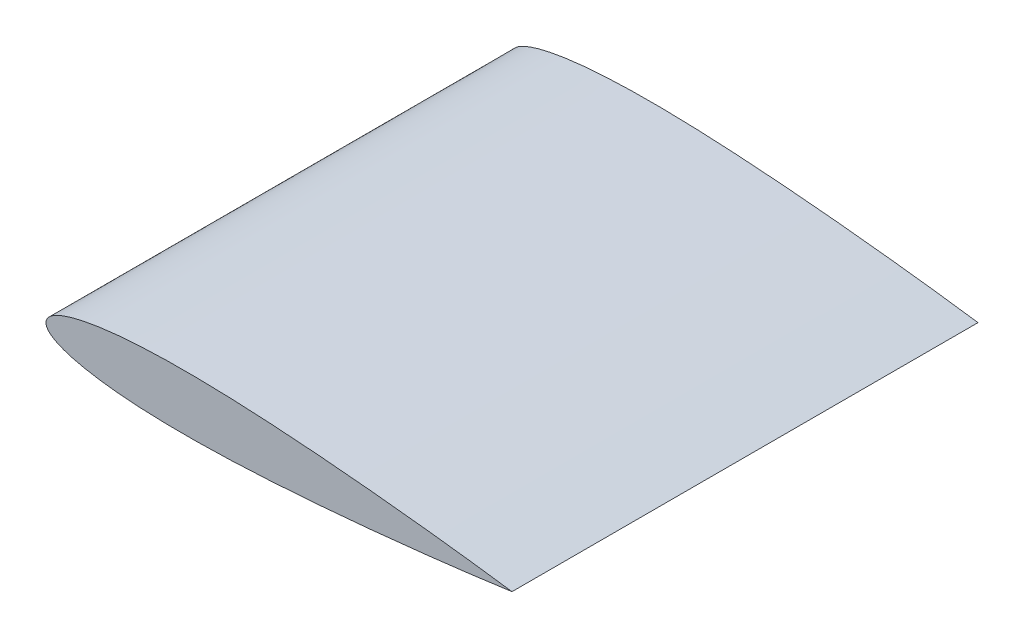
SolidWorks part; units mm, degrees
material "Custom Plastic"
ref_plane "Front Plane" through (0, 0, 0) normal (0, 0, 1) x (1, 0, 0)
ref_plane "Top Plane" through (0, 0, 0) normal (0, 1, 0) x (1, 0, 0)
ref_plane "Right Plane" through (0, 0, 0) normal (1, 0, 0) x (0, 0, -1)
other "Configuration Table"
sketch "Sketch1" plane through (0, 0, 0) normal (0, 0, -1) x (-1, 0, 0)
  spline S0 degree 4 poles (0, 0) (0, 0.0009) (0.0001, 0.0028) (0.0009, 0.006) (0.0029, 0.0097) (0.0068, 0.0145) (0.0126, 0.0192) (0.0211, 0.0244) (0.0349, 0.0306) (0.0554, 0.0375) (0.0898, 0.0455) (0.1398, 0.0529) (0.2034, 0.0579) (0.2766, 0.06) (0.3533, 0.0592) (0.4293, 0.0565) (0.5064, 0.052) (0.5813, 0.0466) (0.6596, 0.0397) (0.7322, 0.0327) (0.814, 0.0237) (0.8804, 0.0161) (0.9794, 0.0031) (1.0221, -0.003) (1.0781, -0.0115) (1.0995, -0.0151) knots 0 0 0 0 0 0.003159 0.007001 0.011626 0.014779 0.024842 0.033543 0.04731 0.068441 0.102186 0.159339 0.227558 0.295777 0.363996 0.432215 0.500435 0.568654 0.636873 0.705092 0.773311 0.84153 0.909749 1 1 1 1 1 construction
  spline S1 degree 4 poles (0, 0) (0, 0.0009) (0.0001, 0.0028) (0.0009, 0.006) (0.0029, 0.0097) (0.0068, 0.0145) (0.0126, 0.0192) (0.0211, 0.0244) (0.0349, 0.0306) (0.0554, 0.0375) (0.0898, 0.0455) (0.1398, 0.0529) (0.2034, 0.0579) (0.2766, 0.06) (0.3533, 0.0592) (0.4293, 0.0565) (0.5064, 0.052) (0.5813, 0.0466) (0.6596, 0.0397) (0.7322, 0.0327) (0.814, 0.0237) (0.8804, 0.0161) (0.9491, 0.0071) (0.9828, 0.0024) (1, 0) knots 0 0 0 0 0 0.003159 0.007001 0.011626 0.014779 0.024842 0.033543 0.04731 0.068441 0.102186 0.159339 0.227558 0.295777 0.363996 0.432215 0.500435 0.568654 0.636873 0.705092 0.773311 0.84153 0.909749 0.909749 0.909749 0.909749 0.909749
  spline S2 degree 4 poles (0, 0) (0, -0.0009) (0.0001, -0.0028) (0.0009, -0.006) (0.0029, -0.0097) (0.0068, -0.0145) (0.0126, -0.0192) (0.0211, -0.0244) (0.0349, -0.0306) (0.0554, -0.0375) (0.0898, -0.0455) (0.1398, -0.0529) (0.2034, -0.0579) (0.2766, -0.06) (0.3533, -0.0592) (0.4293, -0.0565) (0.5064, -0.052) (0.5813, -0.0466) (0.6596, -0.0397) (0.7322, -0.0327) (0.814, -0.0237) (0.8804, -0.0161) (0.9491, -0.0071) (0.9828, -0.0024) (1, 0) knots 0 0 0 0 0 0.003159 0.007001 0.011626 0.014779 0.024842 0.033543 0.04731 0.068441 0.102186 0.159339 0.227558 0.295777 0.363996 0.432215 0.500435 0.568654 0.636873 0.705092 0.773311 0.84153 0.909749 0.909749 0.909749 0.909749 0.909749
extrude "Boss-Extrude1" add sketch "Sketch1" against normal mid plane 1 contours S1 S2
scale "Scale1" bodies to scale 133 scale about origin uniform scaling yes scale factor 1000
mirror "Mirror2" about plane through (0, 0, 0) normal (1, 0, 0) of bodies 134
delete or keep bodies "Body-Delete/Keep 1" type delete bodies bodies 134
move or copy body "Body-Move/Copy1" bodies to move or copy 135 copy no translate (-500, 0, 0) parameters "D1"=500, "D2"=0, "D3"=0
